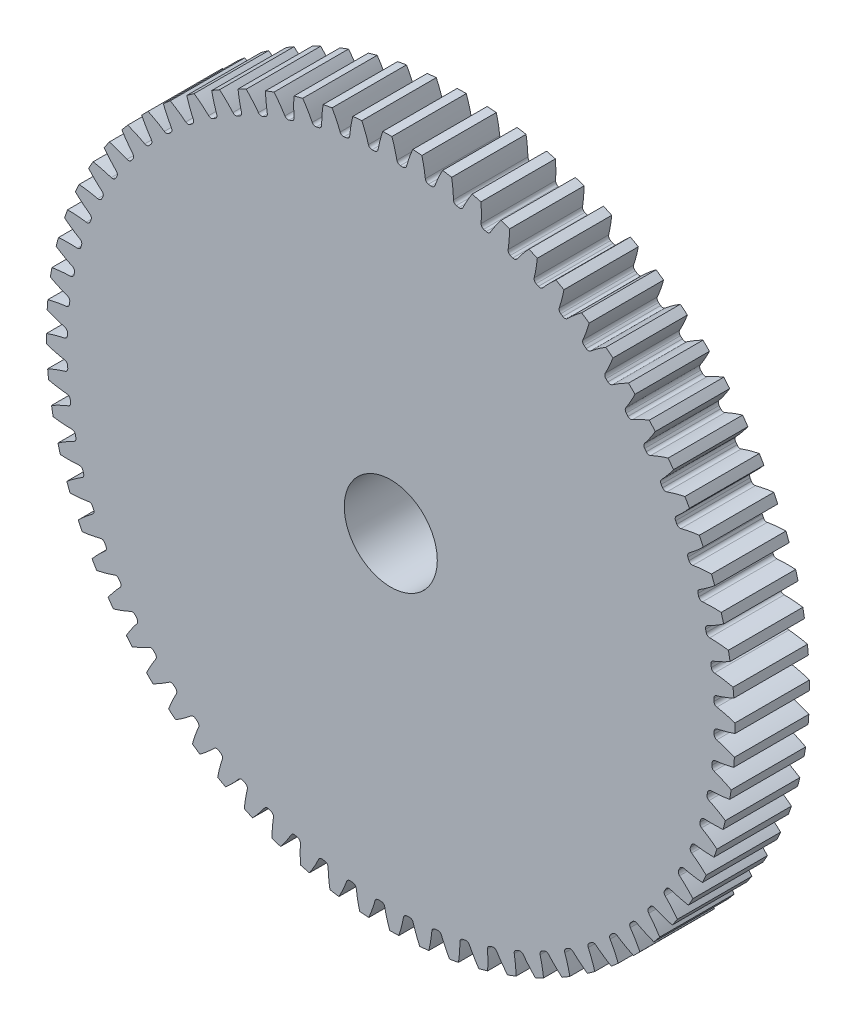
SolidWorks part; units mm, degrees
ref_plane "Front" through (0, 0, 0) normal (0, 0, 1) x (1, 0, 0)
ref_plane "Top" through (0, 0, 0) normal (0, 1, 0) x (1, 0, 0)
ref_plane "Right" through (0, 0, 0) normal (1, 0, 0) x (0, 0, -1)
sketch "Sketch3" plane through (0, 0, 0) normal (0, 0, 1) x (1, 0, 0)
  circle A0 centre (0, 0) radius 58.7375
  dimension "od" = 117.475
extrude "gearBody" add sketch "Sketch3" along normal blind 12.7
sketch "Sketch2" plane through (0, 0, 0) normal (0, 0, 1) x (1, 0, 0)
  line L0 (0, 0) -> (51.1179, 21.1737) construction
  line L1 (69.1321, -13.0587) -> (0, 0) construction
  line L2 (0, 0) -> (36.3143, 0) construction
  line L3 (57.1459, -0.687) -> (57.0634, -3.1445) construction
  line L5 (57.1046, -1.9157) -> (0, 0) construction
  line L7 (0, 0) -> (55.3296, 0) construction
  arc A0 (55.3185, -1.1104) -> (55.2685, -2.5995) centre (0, 0) ccw construction
  arc A1 (58.7372, -0.1845) -> (58.6175, -3.7525) centre (0, 0) ccw construction
  arc A2 (57.1459, -0.687) -> (57.0634, -3.1445) centre (0, 0) ccw construction
  arc A3 (55.1552, -2.0743) -> (55.1702, -1.6269) centre (0, 0) ccw
  arc A4 (69.1321, -13.0587) -> (55.606, -2.6897) centre (49.5839, -24.5521) ccw
  arc A5 (69.1321, -13.0587) -> (69.8518, 8.3961) centre (0, 0) ccw
  arc A6 (69.8518, 8.3961) -> (55.6612, -1.0431) centre (51.1179, 21.1737) cw
  arc A7 (55.1702, -1.6269) -> (55.6612, -1.0431) centre (55.7843, -1.645) cw
  arc A8 (55.606, -2.6897) -> (55.1552, -2.0743) centre (55.7691, -2.0974) cw
  point P6 (69.8518, 8.3961)
  point P22 (69.1321, -13.0587)
  dimension "baseDia" = 110.6593
  dimension "od" = 117.475
  dimension "pd" = 114.3
  dimension "rd" = 110.3884
  dimension "rFillet" = 0.6144
  dimension "pointX" = 69.8518
  dimension "pointY" = 8.3961
  dimension "CTT" = 2.4574
  dimension "flankCenterAngle" = 22.5
extrude "toothCut" cut sketch "Sketch2" along normal through all
pattern_circular "CirPattern1" count 72 over 360 about axis through (0, 0, 12.7) along (0, 0, -1) of "toothCut"
sketch "hub1Dia" plane through (0, 0, 0) normal (0, 0, -1) x (-1, 0, 0)
  circle A0 centre (0, 0) radius 12.7
  dimension "hub1Dia" = 25.4
sketch "hub2Dia" plane through (0, 0, 12.7) normal (0, 0, 1) x (1, 0, 0)
  circle A0 centre (0, 0) radius 12.7
  dimension "hub2dia" = 25.4
sketch "boreDia" plane through (0, 0, 0) normal (0, 0, 1) x (1, 0, 0)
  circle A0 centre (0, 0) radius 7.9375
  dimension "boreDia" = 15.875
extrude "bore" cut sketch "boreDia" against normal mid plane 25400
